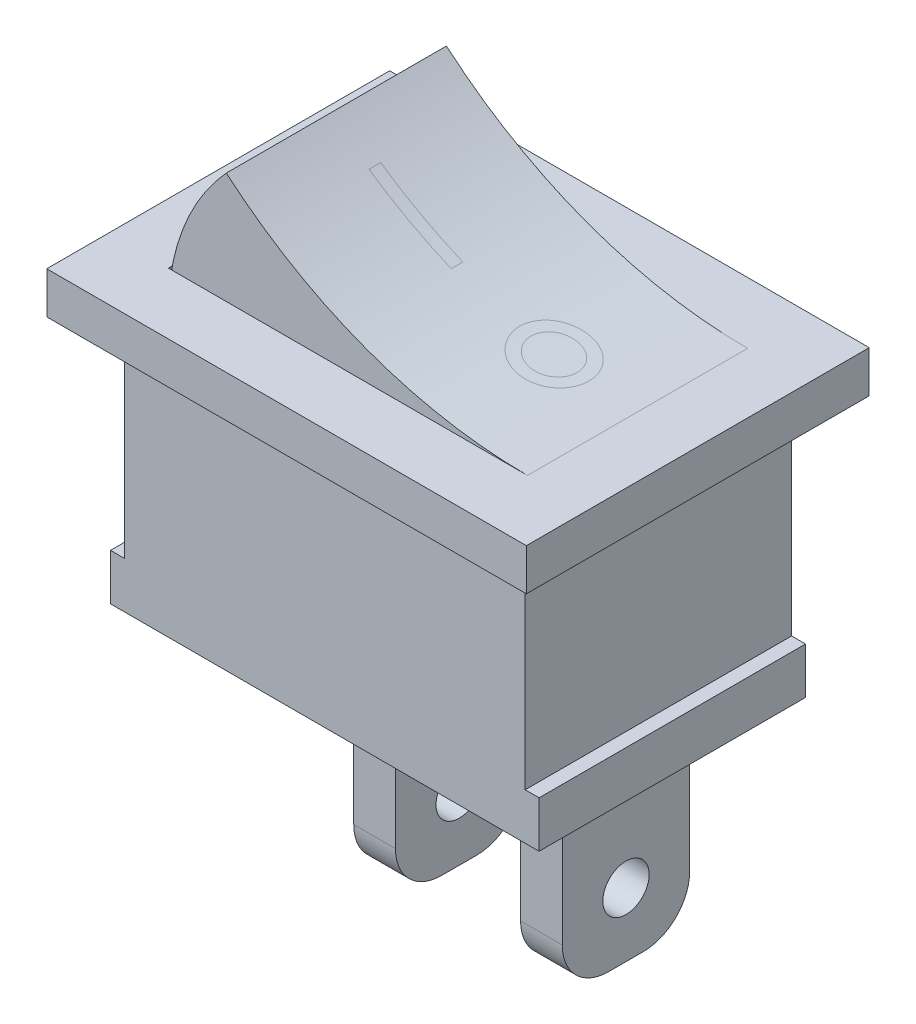
SolidWorks part; units mm, degrees
ref_plane "Alzado" through (0, 0, 0) normal (0, 0, 1) x (1, 0, 0)
ref_plane "Planta" through (0, 0, 0) normal (0, 1, 0) x (1, 0, 0)
ref_plane "Vista lateral" through (0, 0, 0) normal (1, 0, 0) x (0, 0, -1)
sketch "Croquis1" plane through (0, 0, 0) normal (0, 0, 1) x (1, 0, 0)
  line L0 (8.65, -4.5) -> (9.25, -4.5)
  line L1 (-8.65, 4.5) -> (8.65, 4.5)
  line L2 (-8.65, 4.5) -> (-8.65, -4.5)
  line L4 (8.65, 4.5) -> (8.65, -4.5)
  line L5 (-8.65, 4.5) -> (8.65, -4.5) construction
  line L6 (-8.65, -4.5) -> (8.65, 4.5) construction
  line L7 (-9.25, -4.5) -> (-8.65, -4.5)
  line L8 (-9.25, -4.5) -> (-9.25, -6.5)
  line L9 (-9.25, -6.5) -> (9.25, -6.5)
  line L10 (9.25, -4.5) -> (9.25, -6.5)
  point P0 (0, 0)
  point P11 (0, -6.5)
  dimension "D1" = 17.3
  dimension "D2" = 11
  dimension "D3" = 9
  dimension "D4" = 18.5
extrude "Saliente-Extruir1" add sketch "Croquis1" along normal mid plane 11.5
sketch "Croquis2" plane through (0, 4.5, 0) normal (0, 1, 0) x (1, 0, 0)
  line L1 (-10.35, 7.4) -> (10.35, 7.4)
  line L2 (-10.35, 7.4) -> (-10.35, -7.4)
  line L3 (-10.35, -7.4) -> (10.35, -7.4)
  line L4 (10.35, 7.4) -> (10.35, -7.4)
  line L5 (-10.35, 7.4) -> (10.35, -7.4) construction
  line L6 (-10.35, -7.4) -> (10.35, 7.4) construction
  point P0 (0, 0)
  dimension "D1" = 20.7
  dimension "D2" = 14.8
extrude "Saliente-Extruir2" add sketch "Croquis2" along normal blind 1.8
sketch "Croquis3" plane through (0, 6.3, 0) normal (0, 1, 0) x (1, 0, 0)
  line L1 (-7.75, 4.75) -> (7.75, 4.75)
  line L2 (-7.75, 4.75) -> (-7.75, -4.75)
  line L3 (-7.75, -4.75) -> (7.75, -4.75)
  line L4 (7.75, 4.75) -> (7.75, -4.75)
  line L5 (-7.75, 4.75) -> (7.75, -4.75) construction
  line L6 (-7.75, -4.75) -> (7.75, 4.75) construction
  point P0 (0, 0)
  dimension "D1" = 15.5
  dimension "D2" = 9.5
extrude "Cortar-Extruir1" cut sketch "Croquis3" against normal blind 1.8
sketch "Croquis4" plane through (0, 0, 0) normal (0, 0, 1) x (1, 0, 0)
  line L0 (7.75, 4.5) -> (-7.75, 4.5)
  line L1 (7.75, 4.5) -> (7.75, 6.3)
  line L2 (-10.35, 6.3) -> (10.35, 6.3) construction
  arc A0 (7.75, 6.3) -> (-5.25, 11.1013) centre (7.75, 26.3) cw
  arc A1 (-7.75, 4.5) -> (-5.25, 11.1013) centre (1.7484, 4.6769) cw
  dimension "D1" = 9.5
  dimension "D2" = 20
  dimension "D3" = 13
extrude "Saliente-Extruir3" add sketch "Croquis4" along normal up to surface and the other way up to surface separate body up to face at (0, 5.4, 4.75) other way up to face at (0, 5.4, -4.75)
sketch "Croquis5" plane through (0, 0, 0) normal (0, 0, 1) x (1, 0, 0)
  line L0 (-5.25, 11.1013) -> (7.75, 6.3) construction
  line L1 (-10.35, 6.3) -> (10.35, 6.3) construction
ref_plane "Plano1" through (2.9778, 8.0625, 0) normal (-0.3465, -0.9381, 0) x (0.9381, -0.3465, 0)
sketch "Croquis6" plane through (2.9778, 8.0625, 0) normal (-0.3465, -0.9381, 0) x (0.9381, -0.3465, 0)
  line L0 (-8.771, 0) -> (5.0873, 0) construction
  line L1 (-2.771, 0.25) -> (-6.771, 0.25)
  line L2 (-2.771, 0.25) -> (-2.771, -0.25)
  line L3 (-2.771, -0.25) -> (-6.771, -0.25)
  line L4 (-6.771, 0.25) -> (-6.771, -0.25)
  line L5 (-2.771, 0.25) -> (-6.771, -0.25) construction
  line L6 (-2.771, -0.25) -> (-6.771, 0.25) construction
  line L7 (-8.771, 4.75) -> (-8.771, -4.75) construction
  line L8 (5.0873, 4.75) -> (5.0873, -4.75) construction
  circle A0 centre (1.5873, 0) radius 1.5
  circle A1 centre (1.5873, 0) radius 1
  point P0 (-4.771, 0)
  dimension "D4" = 3
  dimension "D1" = 4
  dimension "D2" = 0.5
  dimension "D3" = 2
  dimension "D6" = 3.5
  dimension "D5" = 0.5
split line "Línea de partición1"
sketch "Croquis7" plane through (0, 0, 0) normal (0, 0, 1) x (1, 0, 0)
  line L0 (-9.25, -6.5) -> (9.25, -6.5) construction
  line L1 (5.45, -6.5) -> (7.25, -6.5)
  line L2 (5.45, -6.5) -> (5.45, -14.5)
  line L3 (5.45, -14.5) -> (7.25, -14.5)
  line L4 (7.25, -6.5) -> (7.25, -14.5)
  line L5 (9.25, -6.5) -> (9.25, -4.5) construction
  line L6 (2.75, -6.5) -> (2.75, -14.5) construction
  line L7 (-1.75, -6.5) -> (-1.75, -14.5)
  line L8 (0.05, -14.5) -> (-1.75, -14.5)
  line L9 (0.05, -6.5) -> (0.05, -14.5)
  line L10 (0.05, -6.5) -> (-1.75, -6.5)
  dimension "D1" = 2
  dimension "D2" = 8
  dimension "D3" = 1.8
  dimension "D4" = 5.4
extrude "Saliente-Extruir4" add sketch "Croquis7" along normal mid plane 5.5 separate body
fillet "Redondeo1" radius 2 2 edges at (-0.85, -14.5, -2.75) (-0.85, -14.5, 2.75)
fillet "Redondeo2" radius 2 2 edges at (6.35, -14.5, -2.75) (6.35, -14.5, 2.75)
sketch "Croquis9" plane through (7.25, 0, 0) normal (1, 0, 0) x (0, 0, -1)
  line L0 (-0.75, -14.5) -> (0.75, -14.5) construction
  line L1 (2.75, -12.5) -> (2.75, -6.5) construction
  circle A0 centre (0, -11.7396) radius 1
  dimension "D1" = 2
  dimension "D2" = 2.75
  dimension "D3" = 2.7604
extrude "Cortar-Extruir2" cut sketch "Croquis9" against normal through all
sketch "Croquis10" plane through (0, 0, 0) normal (0, 0, 1) x (1, 0, 0)
  line L1 (-10.35, 4.5) -> (10.35, 4.5) construction
  line L9 (-9.25, -6.5) -> (9.25, -6.5)
  line L10 (-9.25, -6.5) -> (-9.25, 4.5)
  line L11 (-9.25, 4.5) -> (9.25, 4.5)
  line L12 (9.25, -6.5) -> (9.25, 4.5)
  dimension "D1" = 11
  dimension "D2" = 18.5
